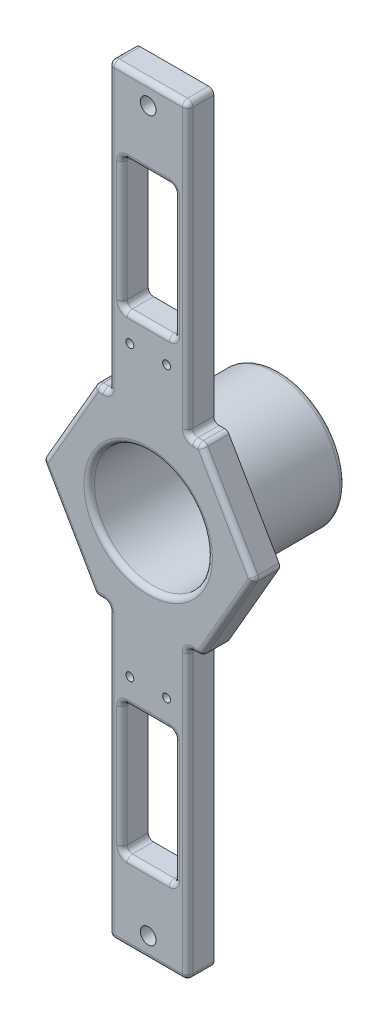
SolidWorks part; units mm, degrees
ref_plane "Спереди" through (0, 0, 0) normal (0, 0, 1) x (1, 0, 0)
ref_plane "Сверху" through (0, 0, 0) normal (0, 1, 0) x (1, 0, 0)
ref_plane "Справа" through (0, 0, 0) normal (1, 0, 0) x (0, 0, -1)
other "Configuration Table"
sketch "Sketch1" plane through (0, 0, 0) normal (0, 0, 1) x (1, 0, 0)
  line L1 (20.2073, 35) -> (-20.2073, 35)
  line L2 (-20.2073, 35) -> (-40.4145, 0)
  line L3 (-40.4145, 0) -> (-20.2073, -35)
  line L4 (-20.2073, -35) -> (20.2073, -35)
  line L5 (20.2073, -35) -> (40.4145, 0)
  line L6 (40.4145, 0) -> (20.2073, 35)
  circle A1 centre (0, 0) radius 35 construction
  dimension "D1" = 70
extrude "Boss-Extrude2" add sketch "Sketch1" along normal blind 10
sketch "Sketch4" plane through (0, 0, 0) normal (0, 0, -1) x (-1, 0, 0)
  line L0 (0, 0) -> (0, 40.6349) construction
  line L1 (-56.6567, 0) -> (54.1025, 0) construction
  line L2 (-20.2073, 35) -> (20.2073, 35) construction
  line L3 (-15, 35) -> (15, 35)
  line L4 (-15, 35) -> (-15, 145)
  line L5 (-15, 145) -> (15, 145)
  line L6 (15, 35) -> (15, 145)
  line L7 (-15, -145) -> (15, -145)
  line L8 (15, -35) -> (15, -145)
  line L9 (-15, -35) -> (15, -35)
  line L10 (-15, -35) -> (-15, -145)
  line L11 (0, 145) -> (0, 121.9848) construction
  circle A0 centre (0, 137) radius 1.5
  circle A1 centre (0, -137) radius 1.5
  dimension "D3" = 3
  dimension "D1" = 30
  dimension "D2" = 110
  dimension "D4" = 137
extrude "Boss-Extrude4" add sketch "Sketch4" against normal up to surface (10 mm away) up to face at (0, 0, 10)
sketch "Sketch5" plane through (0, 0, 10) normal (0, 0, 1) x (1, 0, 0)
  circle A0 centre (0, 137) radius 3
  circle A1 centre (0, -137) radius 3
  dimension "D1" = 6
  dimension "D2" = 6
extrude "Cut-Extrude3" cut sketch "Sketch5" against normal blind 5
sketch "Sketch6" plane through (0, 0, 0) normal (0, 0, -1) x (-1, 0, 0)
  line L0 (-44.6052, 0) -> (88.3819, 0) construction
  line L1 (0, 145) -> (0, 120.7707) construction
  line L2 (15, 145) -> (-15, 145) construction
  line L3 (0, 137) -> (-4.1294, 137) construction
  line L4 (3, 138) -> (7, 138)
  line L5 (-1, 140) -> (1, 140)
  line L6 (-1, 140) -> (-1, 144)
  line L7 (-1, 144) -> (1, 144)
  line L8 (1, 140) -> (1, 144)
  line L9 (-1, 140) -> (1, 144) construction
  line L10 (-1, 144) -> (1, 140) construction
  line L11 (3, 138) -> (3, 136)
  line L12 (3, 136) -> (7, 136)
  line L13 (7, 138) -> (7, 136)
  line L14 (1, 134) -> (1, 130)
  line L15 (1, 134) -> (-1, 134)
  line L16 (-1, 134) -> (-1, 130)
  line L17 (1, 130) -> (-1, 130)
  line L18 (-3, 136) -> (-7, 136)
  line L19 (-3, 136) -> (-3, 138)
  line L20 (-3, 138) -> (-7, 138)
  line L21 (-7, 136) -> (-7, 138)
  line L22 (1, -134) -> (-1, -134)
  line L23 (-1, -134) -> (-1, -130)
  line L24 (1, -130) -> (-1, -130)
  line L25 (1, -134) -> (1, -130)
  line L26 (3, -138) -> (3, -136)
  line L27 (3, -136) -> (7, -136)
  line L28 (7, -138) -> (7, -136)
  line L29 (3, -138) -> (7, -138)
  line L30 (-3, -136) -> (-3, -138)
  line L31 (-3, -138) -> (-7, -138)
  line L32 (-7, -136) -> (-7, -138)
  line L33 (-3, -136) -> (-7, -136)
  line L34 (-1, -144) -> (1, -144)
  line L35 (1, -140) -> (1, -144)
  line L36 (-1, -140) -> (1, -140)
  line L37 (-1, -140) -> (-1, -144)
  point P10 (0, 142)
  point P31 (0, 137)
  dimension "D1" = 4
  dimension "D2" = 2
  dimension "D3" = 3
  dimension "D4" = 4
extrude "Cut-Extrude4" cut sketch "Sketch6" against normal blind 4
sketch "Sketch13" plane through (0, 0, 10) normal (0, 0, 1) x (1, 0, 0)
  line L0 (15, 145) -> (15, 35) construction
  line L1 (10, 65) -> (-10, 65)
  line L2 (10, 65) -> (10, 115)
  line L3 (10, 115) -> (-10, 115)
  line L4 (-10, 65) -> (-10, 115)
  line L5 (10, 65) -> (-10, 115) construction
  line L6 (10, 115) -> (-10, 65) construction
  line L7 (0, 145) -> (0, 62.8418) construction
  line L8 (-15, 145) -> (15, 145) construction
  line L9 (-15, 90) -> (15, 90) construction
  line L10 (-15, 35) -> (-15, 145) construction
  line L11 (-40.4145, 0) -> (62.8003, 0) construction
  line L12 (10, -115) -> (-10, -115)
  line L13 (-10, -65) -> (-10, -115)
  line L14 (10, -65) -> (-10, -65)
  line L15 (10, -65) -> (10, -115)
  point P0 (0, 90)
  dimension "D1" = 5
  dimension "D2" = 50
extrude "Cut-Extrude7" cut sketch "Sketch13" against normal up to next
fillet "Fillet4" radius 2 44 edges at (15, 90, 10) (0, 145, 10) (-15, 90, 10) (-30.3109, 17.5, 10) (-30.3109, -17.5, 10) (15, -90, 10) (30.3109, 17.5, 10) (-15, -90, 10) (0, -145, 10) (30.3109, -17.5, 10) (17.6036, 35, 10) (17.6036, -35, 10) (-17.6036, -35, 10) (-17.6036, 35, 10) (10, -65, 5) (-10, -65, 5) (-10, -115, 5) (10, -115, 5) (-10, 65, 5) (-10, 115, 5) (10, 115, 5) (10, 65, 5) (40.4145, 0, 5) (20.2073, -35, 5) (15, -35, 5) (15, -145, 5) (-15, -145, 5) (-15, -35, 5) (-20.2073, -35, 5) (-40.4145, 0, 5) (-20.2073, 35, 5) (-15, 35, 5) (15, 145, 5) (15, 35, 5) (20.2073, 35, 5) (-15, 145, 5) (0, -115, 10) (0, 115, 10) (10, -90, 10) (-10, -90, 10) (-10, 90, 10) (10, 90, 10) (0, -65, 10) (0, 65, 10)
sketch "Sketch14" plane through (0, 0, 0) normal (0, 0, -1) x (-1, 0, 0)
  circle A0 centre (0, 0) radius 25
  dimension "D1" = 50
extrude "Boss-Extrude5" add sketch "Sketch14" along normal blind 40
sketch "Sketch15" plane through (0, 0, 10) normal (0, 0, 1) x (1, 0, 0)
  circle A0 centre (0, 0) radius 22.5
  dimension "D1" = 45
extrude "Cut-Extrude8" cut sketch "Sketch15" against normal offset from surface (45 mm away) 5 up to face at (-25, 0, -40)
sketch "Sketch16" plane through (0, 0, -40) normal (0, 0, -1) x (-1, 0, 0)
  circle A0 centre (0, 0) radius 9
  dimension "D1" = 18
extrude "Cut-Extrude9" cut sketch "Sketch16" against normal up to next
sketch "Sketch17" plane through (0, 0, -40) normal (0, 0, -1) x (-1, 0, 0)
  line L0 (-44.5312, 0) -> (54.6996, 0) construction
  line L1 (0, 0) -> (0, 13.5892) construction
  circle A0 centre (-14.5, 0) radius 2
  circle A1 centre (14.5, 0) radius 2
  dimension "D1" = 4
  dimension "D2" = 29
extrude "Cut-Extrude10" cut sketch "Sketch17" against normal up to next
fillet "Fillet5" radius 2 1 edges at (-25, 0, -40)
fillet "Fillet6" radius 2 1 edges at (22.5, 0, 10)
sketch "Sketch18" plane through (0, 0, -40) normal (0, 0, -1) x (-1, 0, 0)
  line L0 (0, 0) -> (24.123, 24.123) construction
  line L1 (7.5831, 14.6542) -> (0, 0) construction
  line L2 (0, 0) -> (14.6542, 7.5831) construction
  line L3 (14.6542, 7.5831) -> (11.1017, 5.7448)
  line L4 (7.5831, 14.6542) -> (5.7448, 11.1017)
  line L5 (0, 0) -> (49.2355, 0) construction
  line L6 (14.6542, -7.5831) -> (11.1017, -5.7448)
  line L7 (7.5831, -14.6542) -> (5.7448, -11.1017)
  line L8 (-7.5831, -14.6542) -> (-5.7448, -11.1017)
  line L9 (-14.6542, -7.5831) -> (-11.1017, -5.7448)
  line L10 (-14.6542, 7.5831) -> (-11.1017, 5.7448)
  line L11 (-7.5831, 14.6542) -> (-5.7448, 11.1017)
  arc A0 (7.5831, 14.6542) -> (14.6542, 7.5831) centre (0, 0) cw
  arc A1 (5.7448, 11.1017) -> (11.1017, 5.7448) centre (0, 0) cw
  arc A2 (11.1017, -5.7448) -> (5.7448, -11.1017) centre (0, 0) cw
  arc A3 (14.6542, -7.5831) -> (7.5831, -14.6542) centre (0, 0) cw
  arc A4 (-5.7448, -11.1017) -> (-11.1017, -5.7448) centre (0, 0) cw
  arc A5 (-7.5831, -14.6542) -> (-14.6542, -7.5831) centre (0, 0) cw
  arc A6 (-11.1017, 5.7448) -> (-5.7448, 11.1017) centre (0, 0) cw
  arc A7 (-14.6542, 7.5831) -> (-7.5831, 14.6542) centre (0, 0) cw
  point P23 (0, 0)
  dimension "D1" = 16.5
  dimension "D2" = 12.5
  dimension "D3" = 10
  dimension "D4" = 45
  dimension "D5" = 4
extrude "Cut-Extrude11" cut sketch "Sketch18" against normal up to next
sketch "Sketch19" plane through (0, 0, 10) normal (0, 0, 1) x (1, 0, 0)
  line L0 (-54.9132, 0) -> (94.5139, 0) construction
  line L1 (-7, 55) -> (7, 55) construction
  line L2 (0, 0) -> (0, 76.9882) construction
  circle A0 centre (-7, 55) radius 1.5
  circle A1 centre (7, 55) radius 1.5
  circle A2 centre (7, -55) radius 1.5
  circle A3 centre (-7, -55) radius 1.5
  dimension "D1" = 3
  dimension "D2" = 14
  dimension "D3" = 110
extrude "Cut-Extrude12" cut sketch "Sketch19" against normal up to next
sketch "Sketch20" plane through (0, 0, 0) normal (0, 0, -1) x (-1, 0, 0)
  circle A0 centre (-7, -55) radius 3
  circle A1 centre (7, -55) radius 3
  circle A2 centre (-7, 55) radius 3
  circle A3 centre (7, 55) radius 3
  dimension "D1" = 6
extrude "Cut-Extrude13" cut sketch "Sketch20" against normal blind 5
